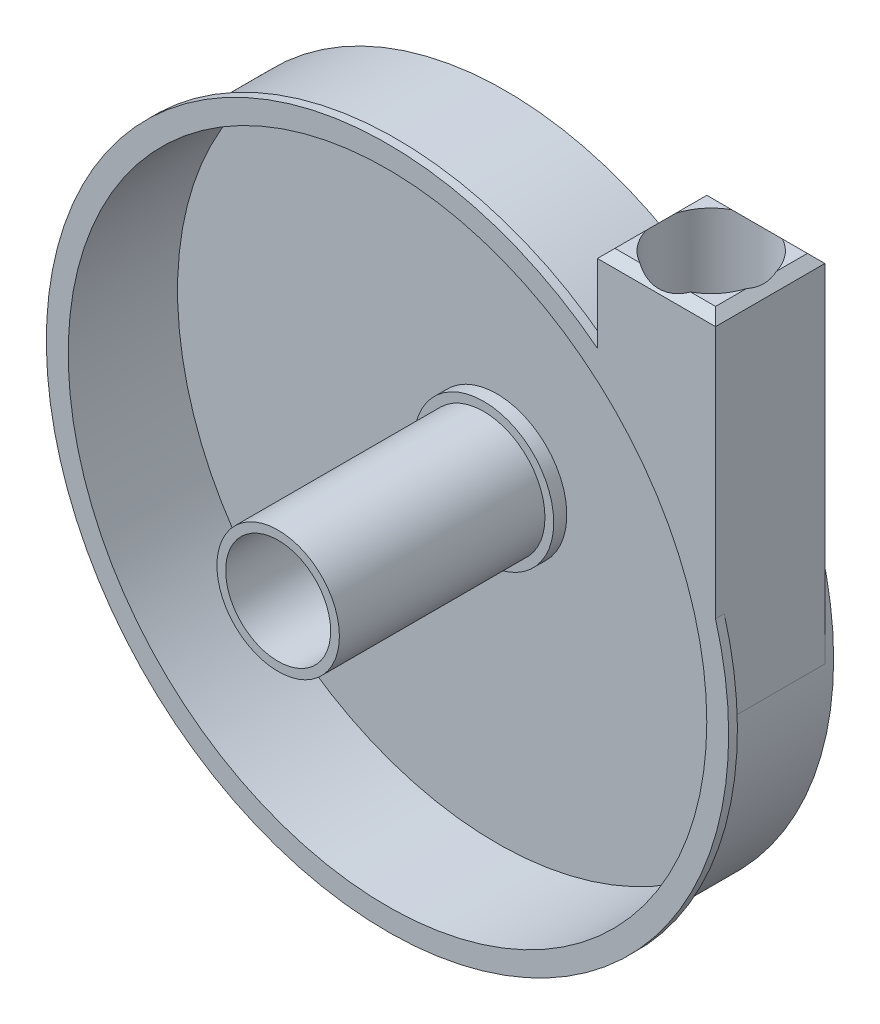
SolidWorks part; units mm, degrees
ref_plane "Front Plane" through (0, 0, 0) normal (0, 0, 1) x (1, 0, 0)
ref_plane "Top Plane" through (0, 0, 0) normal (0, 1, 0) x (1, 0, 0)
ref_plane "Right Plane" through (0, 0, 0) normal (1, 0, 0) x (0, 0, -1)
sketch "Sketch1" plane through (0, 0, 0) normal (0, 0, 1) x (1, 0, 0)
  circle A0 centre (0, 0) radius 75
  circle A1 centre (0, 0) radius 73
extrude "Boss-Extrude1" add sketch "Sketch1" along normal blind 25
sketch "Sketch2" plane through (0, 0, 25) normal (0, 0, 1) x (1, 0, 0)
  line L0 (48, 81.2871) -> (48, 57.6281)
  line L1 (75, 0) -> (75, 81.2871)
  line L2 (75, 81.2871) -> (48, 81.2871)
  circle A3 centre (0, 0) radius 75 construction
  arc A4 (75, 0) -> (48, 57.6281) centre (0, 0) ccw
  circle A5 centre (0, 0) radius 75
  arc A6 (48, 57.6281) -> (75, 0) centre (0, 0) ccw
  dimension "D1" = 0
extrude "Boss-Extrude2" add sketch "Sketch2" against normal up to surface (25 mm away) up to face at (75, 0, 0)
sketch "Sketch4" plane through (0, 81.2871, 0) normal (0, 1, 0) x (1, 0, 0)
  circle A0 centre (61.5, -12.5) radius 12
extrude "Cut-Extrude2" cut sketch "Sketch4" against normal blind 81
sketch "Sketch5" plane through (0, 0, 0) normal (0, 0, -1) x (-1, 0, 0)
  circle A0 centre (0, 0) radius 75
  circle A1 centre (0, 0) radius 12
extrude "Boss-Extrude3" add sketch "Sketch5" along normal blind 2
chamfer "Chamfer1" distance 2 angle 45 4 edges at (61.5, 81.2871, 0) (61.5, 81.2871, 25) (75, 81.2871, 12.5) (48, 81.2871, 12.5)
sketch "Sketch6" plane through (0, 0, 0) normal (0, 0, 1) x (1, 0, 0)
  circle A0 centre (0, 0) radius 12
  circle A1 centre (0, 0) radius 14
extrude "Boss-Extrude4" add sketch "Sketch6" along normal blind 50
sketch "Sketch7" plane through (0, 0, 0) normal (0, 0, 1) x (1, 0, 0)
  circle A0 centre (0, 0) radius 16
  circle A1 centre (0, 0) radius 14
extrude "Boss-Extrude5" add sketch "Sketch7" along normal blind 3
sketch "Sketch8" plane through (0, 0, 25) normal (0, 0, 1) x (1, 0, 0)
  circle A0 centre (0, 0) radius 75
  circle A1 centre (0, 0) radius 78
extrude "Boss-Extrude6" add sketch "Sketch8" against normal blind 2
